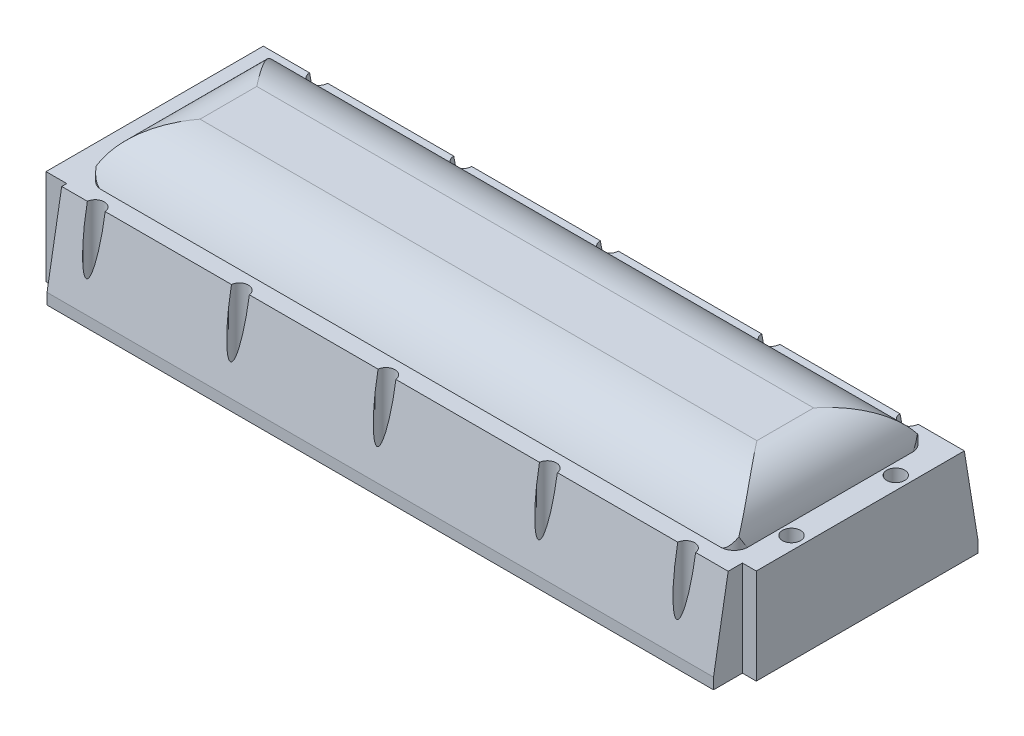
SolidWorks part; units mm, degrees
ref_plane "Alzado" through (0, 0, 0) normal (0, 0, 1) x (1, 0, 0)
ref_plane "Planta" through (0, 0, 0) normal (0, 1, 0) x (1, 0, 0)
ref_plane "Vista lateral" through (0, 0, 0) normal (1, 0, 0) x (0, 0, -1)
sketch "Croquis2" plane through (0, 0, 0) normal (0, 1, 0) x (1, 0, 0)
  line L0 (-256, 14.25) -> (-256, 181.28)
  line L1 (-256, 181.28) -> (251, 181.28)
  line L2 (251, 181.28) -> (251, 20.92)
  line L3 (241, 0) -> (-241, 0)
  line L7 (-256, 14.25) -> (-241, 14.25)
  line L8 (-241, 0) -> (-241, 14.25)
  line L11 (251, 20.92) -> (241, 20.92)
  line L12 (241, 0) -> (241, 20.92)
  point P0 (0, 0)
  dimension "D1" = 181.28
  dimension "D2" = 507
  dimension "D3" = 14.25
  dimension "D4" = 15
  dimension "D5" = 20.92
  dimension "D6" = 10
extrude "Saliente-Extruir1" add sketch "Croquis2" along normal blind 100
sketch "Croquis3" plane through (-256, 0, 0) normal (-1, 0, 0) x (0, 0, 1)
  line L0 (-181.28, 0) -> (-14.25, 0) construction
  line L2 (-20.92, 100) -> (-22.91, 100)
  line L3 (-181.28, 100) -> (-181.28, 0) construction
  line L4 (-181.28, 8) -> (-161.67, 8)
  line L5 (-161.67, 8) -> (-161.67, 100)
  line L6 (-181.28, 100) -> (-14.25, 100) construction
  line L7 (-161.67, 100) -> (-181.28, 100)
  line L8 (-181.28, 100) -> (-181.28, 8)
  line L9 (0, 8) -> (-22.91, 8)
  line L10 (0, 100) -> (0, 0) construction
  line L11 (-22.91, 8) -> (-22.91, 100)
  line L12 (-20.92, 100) -> (0, 100)
  line L13 (0, 100) -> (0, 8)
  line L14 (-181.28, 100) -> (-181.28, 8)
  line M8 (-14.25, 0) -> (-14.25, 100)
  line M9 (-14.25, 100) -> (-181.28, 100)
  line M10 (-181.28, 100) -> (-181.28, 0)
  dimension "D1" = 8
  dimension "D2" = 19.61
  dimension "D4" = 22.91
extrude "Cortar-Extruir2" cut sketch "Croquis3" against normal blind 1047 contours L4 L5 M9 M10 | L13 L12 L9 M8 | L11 L9 M8 M9
sketch "Croquis4" plane through (0, 0, -161.67) normal (0, 0, -1) x (-1, 0, 0)
  line L0 (234.6, 8) -> (234.6, 100)
  line L1 (-251, 8) -> (256, 8) construction
  line L2 (-251, 100) -> (256, 100) construction
  line L3 (234.6, 100) -> (256, 100)
  line L4 (256, 100) -> (256, 8)
  line L5 (256, 8) -> (234.6, 8)
  line L6 (234.6, 8) -> (234.8741, 7.7303)
  line M3 (-251, 8) -> (256, 8)
  line M4 (256, 8) -> (256, 100)
  line M5 (256, 100) -> (-251, 100)
  dimension "D1" = 21.4
extrude "Cortar-Extruir3" cut sketch "Croquis4" against normal blind 1047 contours L0 M3 M4 M5
sketch "Croquis5" plane through (0, 0, -161.67) normal (0, 0, -1) x (-1, 0, 0)
  line L0 (-251, 100) -> (234.6, 100) construction
  line L1 (-251, 8) -> (-233.06, 8)
  line L2 (-251, 8) -> (-251, 100)
  line L3 (-251, 100) -> (-233.06, 100)
  line L4 (-233.06, 8) -> (-233.06, 100)
  dimension "D1" = 17.94
extrude "Cortar-Extruir4" cut sketch "Croquis5" against normal blind 1047
sketch "Croquis6" plane through (0, 0, 0) normal (0, -1, 0) x (1, 0, 0)
  line L0 (-233.6, -160.67) -> (232.06, -160.67)
  line L1 (232.06, -160.67) -> (232.06, -23.91)
  line L2 (232.06, -23.91) -> (-233.6, -23.91)
  line L3 (-233.6, -23.91) -> (-233.6, -160.67)
  line L4 (233.06, -22.91) -> (-234.6, -22.91)
  line L5 (233.06, -161.67) -> (233.06, -22.91)
  line L6 (-234.6, -161.67) -> (233.06, -161.67)
  line L7 (-234.6, -22.91) -> (-234.6, -161.67)
  line L8 (233.06, -22.91) -> (-234.6, -22.91) construction
  line L9 (233.06, -161.67) -> (233.06, -22.91) construction
  line L10 (-234.6, -161.67) -> (233.06, -161.67) construction
  line L11 (-234.6, -22.91) -> (-234.6, -161.67) construction
  dimension "D1" = 0
  dimension "D2" = 1
extrude "Cortar-Extruir5" cut sketch "Croquis6" against normal blind 65
sketch "Croquis7" plane through (0, 8, 0) normal (0, 1, 0) x (1, 0, 0)
  line L0 (-256, 181.28) -> (-256, 14.25) construction
  line L1 (251, 181.28) -> (-256, 181.28) construction
  line L2 (251, 181.28) -> (251, 20.92) construction
  line L3 (241, 20.92) -> (251, 20.92) construction
  line L4 (241, 0) -> (-241, 0) construction
  point P0 (-216, 9.875)
  point P1 (-111.75, 9.875)
  point P2 (-5.75, 9.875)
  point P3 (111, 9.875)
  point P4 (211, 9.875)
  point P5 (241.5, 55.92)
  point P6 (241.5, 131.28)
  point P7 (211, 171.405)
  point P8 (111, 171.405)
  point P9 (-5.75, 171.405)
  point P10 (-111.75, 171.405)
  point P11 (-216, 171.405)
  dimension "D1" = 40
  dimension "D2" = 50
  dimension "D4" = 9.875
  dimension "D5" = 9.5
  dimension "D6" = 35
  dimension "D7" = 40
  dimension "D8" = 100
  dimension "D9" = 116.75
  dimension "D10" = 106
  dimension "D11" = 9.875
hole_wizard "Refrentado para perno con cabeza hexagonal de M101" positions "Croquis3D1" profile "Croquis10" counterbore size "M10" standard "Ansi Metric"
sketch3d "Croquis3D1"
  point P0 (-216, 8, -9.875)
  point P3 (-111.75, 8, -9.875)
  point P6 (-5.75, 8, -9.875)
  point P9 (111, 8, -9.875)
  point P12 (211, 8, -9.875)
  point P15 (241.5, 8, -55.92)
  point P18 (241.5, 8, -131.28)
  point P21 (211, 8, -171.405)
  point P24 (111, 8, -171.405)
  point P27 (-5.75, 8, -171.405)
  point P30 (-111.75, 8, -171.405)
  point P33 (-216, 8, -171.405)
sketch "Croquis10" plane through (-216, 8, -9.875) normal (1, 0, 0) x (0, 0, 1)
  line L0 (0, 0) -> (0, 93.1545)
  line L1 (0, 93.1545) -> (5.25, 90)
  line L2 (5.25, 90) -> (5.25, 6.85)
  line L3 (5.25, 6.85) -> (6.5, 6.85)
  line L4 (6.5, 6.85) -> (6.5, 0)
  line L5 (6.5, 0) -> (0, 0)
  line L10 (0, 93.1545) -> (-5.25, 90) construction
  line L11 (0, -6.35) -> (0, 107.95) construction
  dimension "Diámetro de taladro" = 10.5
  dimension "Profundidad de taladro" = 90
  dimension "Diámetro de refrentado" = 13
  dimension "Profundidad de refrentado" = 6.85
  dimension "Ángulo de perforador" = 118
sketch "Croquis11" plane through (-234.6, 0, 0) normal (-1, 0, 0) x (0, 0, 1)
  line L3 (-181.28, 0) -> (-14.25, 0) construction
  line L4 (-181.28, 8) -> (-181.28, 0) construction
  circle A0 centre (-136.94, 22) radius 8.5
  circle A1 centre (-50.94, 22) radius 8.5
  dimension "D3" = 17
  dimension "D2" = 86
  dimension "D1" = 44.34
  dimension "D4" = 22
extrude "Cortar-Extruir6" cut sketch "Croquis11" against normal blind 211
sketch "Croquis12" plane through (-234.6, 0, 0) normal (-1, 0, 0) x (0, 0, 1)
  line L0 (-181.28, 0) -> (-14.25, 0) construction
  line L1 (-161.67, 8) -> (-161.67, 100) construction
  line L2 (-22.91, 100) -> (-22.91, 8) construction
  line L4 (-22.91, 100) -> (-161.67, 100) construction
  line L5 (-71.7669, 100) -> (-112.8131, 100)
  line L6 (-161.67, 69) -> (-161.67, 100)
  line L7 (-22.91, 100) -> (-161.67, 100)
  line L8 (-22.91, 100) -> (-22.91, 69)
  arc A0 (-112.8131, 100) -> (-161.67, 69) centre (-112.8131, 46) ccw
  arc A1 (-22.91, 69) -> (-71.7669, 100) centre (-71.7669, 46) ccw
  line M4 (-22.91, 100) -> (-161.67, 100)
  line M5 (-161.67, 100) -> (-161.67, 8)
  line M7 (-22.91, 8) -> (-22.91, 100)
  dimension "D2" = 108
  dimension "D3" = 69
  dimension "D1" = 69
extrude "Cortar-Extruir7" cut sketch "Croquis12" against normal through all contours A0 M4 M5 | A1 M7 M4
sketch "Croquis13" plane through (0, 0, -161.67) normal (0, 0, -1) x (-1, 0, 0)
  line L0 (-233.06, 100) -> (234.6, 100) construction
  line L1 (-200.5946, 100) -> (-233.06, 100)
  line L5 (-233.06, 100) -> (-233.06, 69)
  line L6 (-233.06, 69) -> (234.6, 69)
  line L7 (234.6, 69) -> (234.6, 100)
  line L8 (234.6, 100) -> (-233.06, 100)
  line L9 (-233.06, 100) -> (-233.06, 69)
  line L11 (234.6, 69) -> (234.6, 100)
  line L12 (234.6, 100) -> (202.1346, 100)
  arc A0 (-200.5946, 100) -> (-233.06, 69) centre (-200.5946, 67.5) ccw
  arc A1 (234.6, 69) -> (202.1346, 100) centre (202.1346, 67.5) ccw
  dimension "D1" = 65
  dimension "D2" = 0
extrude "Cortar-Extruir9" cut sketch "Croquis13" against normal blind 211
fillet "Redondeo1" radius 10 3 edges at (-233.6, 65, -92.29) (-233.6, 32.5, -160.67) (-233.6, 32.5, -23.91)
fillet "Redondeo2" radius 10 1 edges at (232.06, 32.5, -23.91)
fillet "Redondeo3" radius 10 1 edges at (232.06, 32.5, -160.67)
fillet "Redondeo4" radius 10 7 edges at (-0.77, 65, -160.67) (-230.6711, 62.0711, -26.8389) (-230.6711, 62.0711, -157.7411) (-0.77, 65, -23.91) (229.1311, 65, -26.8389) (232.06, 65, -92.29) (229.1311, 65, -157.7411)
chamfer "Chaflán1" distance 1 angle 45 2 edges at (-233.6, 22, -128.44) (-233.6, 22, -42.44)
fillet "Redondeo5" radius 10 4 edges at (-234.6, 38.5, -161.67) (-234.6, 38.5, -22.91) (233.06, 38.5, -22.91) (233.06, 38.5, -161.67)
sketch "Croquis14" plane through (0, 8, 0) normal (0, 1, 0) x (1, 0, 0)
  line L0 (223.06, 22.91) -> (-224.6, 22.91) construction
  line L1 (233.06, 32.91) -> (233.06, 151.67) construction
  line L2 (223.06, 161.67) -> (-224.6, 161.67) construction
  line L3 (-234.6, 32.91) -> (-234.6, 151.67) construction
  line L4 (-234.6, 32.91) -> (-234.6, 151.67)
  line L5 (223.06, 161.67) -> (-224.6, 161.67)
  line L6 (233.06, 32.91) -> (233.06, 151.67)
  line L7 (223.06, 22.91) -> (-224.6, 22.91)
  line L8 (-241, 14.25) -> (-241, 0)
  line L9 (-241, 0) -> (241, 0)
  line L10 (241, 0) -> (241, 20.92)
  line L11 (241, 20.92) -> (251, 20.92)
  line L12 (251, 20.92) -> (251, 181.28)
  line L13 (251, 181.28) -> (-256, 181.28)
  line L14 (-256, 181.28) -> (-256, 14.25)
  line L15 (-256, 14.25) -> (-241, 14.25)
  line L16 (-241, 14.25) -> (-241, 0)
  line L17 (-241, 0) -> (241, 0)
  line L18 (241, 0) -> (241, 20.92)
  line L19 (241, 20.92) -> (251, 20.92)
  line L20 (251, 20.92) -> (251, 181.28)
  line L21 (251, 181.28) -> (-256, 181.28)
  line L22 (-256, 181.28) -> (-256, 14.25)
  line L23 (-256, 14.25) -> (-241, 14.25)
  arc A0 (223.06, 22.91) -> (233.06, 32.91) centre (223.06, 32.91) ccw construction
  arc A1 (233.06, 151.67) -> (223.06, 161.67) centre (223.06, 151.67) ccw construction
  arc A2 (-224.6, 161.67) -> (-234.6, 151.67) centre (-224.6, 151.67) ccw construction
  arc A3 (-234.6, 32.91) -> (-224.6, 22.91) centre (-224.6, 32.91) ccw construction
  arc A4 (-234.6, 32.91) -> (-224.6, 22.91) centre (-224.6, 32.91) ccw
  arc A5 (-224.6, 161.67) -> (-234.6, 151.67) centre (-224.6, 151.67) ccw
  arc A6 (233.06, 151.67) -> (223.06, 161.67) centre (223.06, 151.67) ccw
  arc A7 (223.06, 22.91) -> (233.06, 32.91) centre (223.06, 32.91) ccw
  circle A8 centre (-216, 9.875) radius 6.5 construction
  circle A9 centre (-216, 171.405) radius 6.5 construction
  circle A10 centre (-111.75, 171.405) radius 6.5 construction
  circle A11 centre (-5.75, 171.405) radius 6.5 construction
  circle A12 centre (111, 171.405) radius 6.5 construction
  circle A13 centre (211, 171.405) radius 6.5 construction
  circle A14 centre (241.5, 131.28) radius 6.5 construction
  circle A15 centre (241.5, 55.92) radius 6.5 construction
  circle A16 centre (-216, 9.875) radius 6.5
  circle A17 centre (-216, 171.405) radius 6.5
  circle A18 centre (-111.75, 171.405) radius 6.5
  circle A19 centre (-5.75, 171.405) radius 6.5
  circle A20 centre (111, 171.405) radius 6.5
  circle A21 centre (211, 171.405) radius 6.5
  circle A22 centre (241.5, 131.28) radius 6.5
  circle A23 centre (241.5, 55.92) radius 6.5
  circle A28 centre (211, 9.875) radius 6.5 construction
  circle A29 centre (111, 9.875) radius 6.5 construction
  circle A30 centre (-5.75, 9.875) radius 6.5 construction
  circle A31 centre (-111.75, 9.875) radius 6.5 construction
  circle A32 centre (211, 9.875) radius 6.5
  circle A33 centre (111, 9.875) radius 6.5
  circle A34 centre (-5.75, 9.875) radius 6.5
  circle A35 centre (-111.75, 9.875) radius 6.5
  dimension "D1" = 0
extrude "Saliente-Extruir2" add sketch "Croquis14" along normal blind 61
sketch "Croquis15" plane through (241, 0, 0) normal (1, 0, 0) x (0, 0, -1)
  line L0 (0, 69) -> (0, 0) construction
  line L1 (10.6044, 69) -> (0, 69)
  line L2 (10.6044, 69) -> (0, 8)
  line L3 (0, 69) -> (20.92, 69) construction
  line L4 (0, 69) -> (0, 0) construction
  line L5 (0, 69) -> (0, -17.0522)
  line L6 (0, -17.0522) -> (3.1889, 6.3179)
  dimension "D1" = 8
  dimension "D2" = 10.6044
extrude "Cortar-Extruir10" cut sketch "Croquis15" against normal blind 550
sketch "Croquis16" plane through (251, 0, 0) normal (1, 0, 0) x (0, 0, -1)
  line L0 (181.28, 69) -> (181.28, 0) construction
  line L1 (171.405, 69) -> (181.28, 69)
  line L2 (171.405, 69) -> (181.28, 8)
  line L3 (181.28, 69) -> (181.28, 0) construction
  line L4 (181.28, 69) -> (181.28, 8)
  line L5 (20.92, 69) -> (181.28, 69) construction
  line L7 (20.92, 0) -> (181.28, 0) construction
  dimension "D1" = 8
  dimension "D2" = 9.875
extrude "Cortar-Extruir11" cut sketch "Croquis16" against normal blind 550
sketch "Croquis18" plane through (-234.6, 0, 0) normal (1, 0, 0) x (0, 0, -1)
  circle A2 centre (136.94, 22) radius 8.5
  circle A3 centre (50.94, 22) radius 8.5
extrude "Cortar-Extruir12" cut sketch "Croquis18" against normal blind 550
